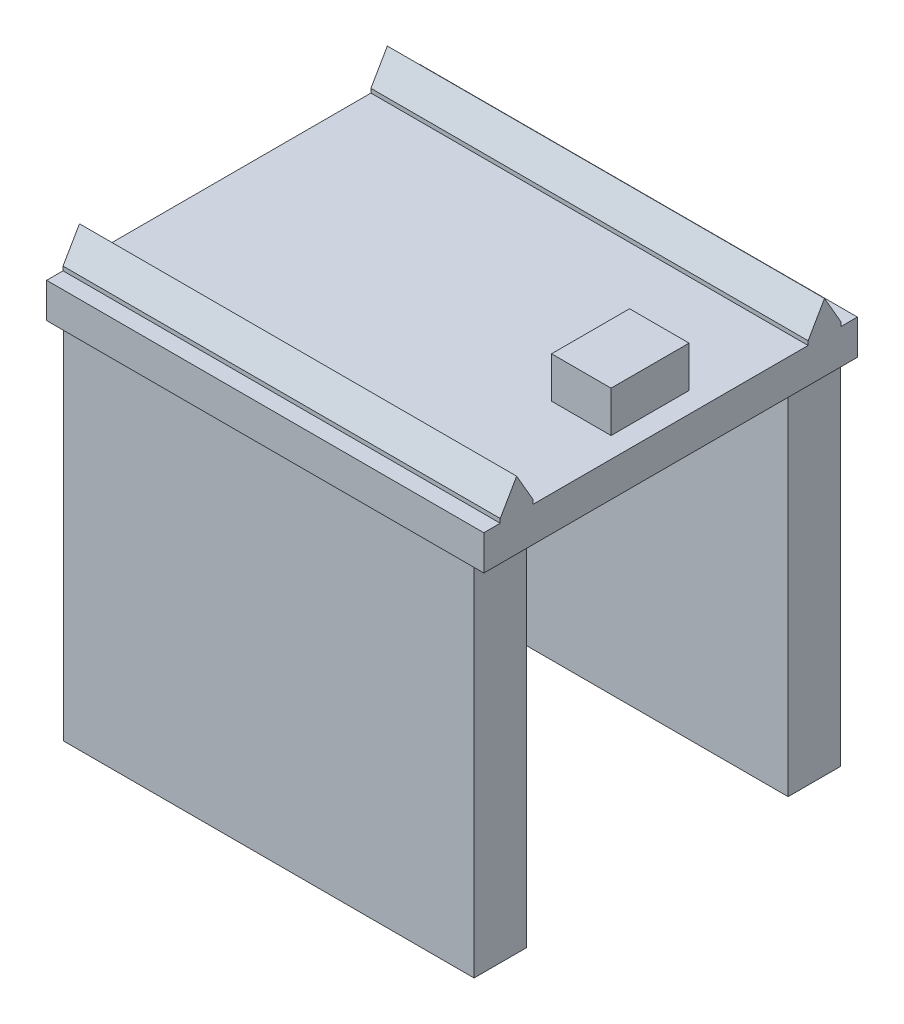
SolidWorks part; units mm, degrees
ref_plane "前视基准面" through (0, 0, 0) normal (0, 0, 1) x (1, 0, 0)
ref_plane "上视基准面" through (0, 0, 0) normal (0, 1, 0) x (1, 0, 0)
ref_plane "右视基准面" through (0, 0, 0) normal (1, 0, 0) x (0, 0, -1)
sketch "草图2" plane through (0, 0, 0) normal (0, 1, 0) x (1, 0, 0)
  line L1 (-10.65, 9.1) -> (10.65, 9.1)
  line L2 (-10.65, 9.1) -> (-10.65, -9.1)
  line L3 (-10.65, -9.1) -> (10.65, -9.1)
  line L4 (10.65, 9.1) -> (10.65, -9.1)
  line L5 (-10.65, 9.1) -> (10.65, -9.1) construction
  line L6 (-10.65, -9.1) -> (10.65, 9.1) construction
  point P0 (0, 0)
  dimension "D1" = 21.3
  dimension "D2" = 18.2
extrude "凸台-拉伸1" add sketch "草图2" along normal blind 1.7
sketch "草图4" plane through (0, 1.7, 0) normal (0, 1, 0) x (1, 0, 0)
  line L0 (-10.65, 9.1) -> (-10.65, -9.1) construction
  line L1 (-10.65, 8.3) -> (10.65, 8.3)
  line L2 (-10.65, 8.3) -> (-10.65, 6.7)
  line L3 (-10.65, 6.7) -> (10.65, 6.7)
  line L4 (10.65, 8.3) -> (10.65, 6.7)
  line L5 (10.65, -9.1) -> (10.65, 9.1) construction
  line L6 (0, 0) -> (10.65, 0) construction
  line L7 (10.65, 9.1) -> (-10.65, 9.1) construction
  line L8 (-10.65, -6.7) -> (10.65, -6.7)
  line L9 (10.65, -8.3) -> (10.65, -6.7)
  line L10 (-10.65, -8.3) -> (10.65, -8.3)
  line L11 (-10.65, -8.3) -> (-10.65, -6.7)
  dimension "D1" = 0.8
  dimension "D2" = 1.6
extrude "凸台-拉伸2" add sketch "草图4" along normal blind 1.6
chamfer "倒角1" distance 1.4 angle 30 4 edges at (0, 3.3, 8.3) (0, 3.3, 6.7) (0, 3.3, -6.7) (0, 3.3, -8.3) first distance on face at (0, 2.5, 8.3) first distance on face at (0, 2.5, 6.7) first distance on face at (0, 2.5, -6.7) first distance on face at (0, 2.5, -8.3)
sketch "草图5" plane through (0, 1.7, 0) normal (0, 1, 0) x (1, 0, 0)
  line L0 (0, 0) -> (10.65, 0) construction
  line L1 (10.65, -6.7) -> (10.65, 6.7) construction
  line L3 (6.75, 1.9) -> (9.65, 1.9)
  line L4 (6.75, 1.9) -> (6.75, -1.9)
  line L5 (6.75, -1.9) -> (9.65, -1.9)
  line L6 (9.65, 1.9) -> (9.65, -1.9)
  line L7 (6.75, 1.9) -> (9.65, -1.9) construction
  line L8 (6.75, -1.9) -> (9.65, 1.9) construction
  point P5 (8.2, 0)
  dimension "D1" = 2.9
  dimension "D2" = 3.8
  dimension "D3" = 3.9
extrude "凸台-拉伸3" add sketch "草图5" along normal blind 2
sketch "草图6" plane through (0, 0, 0) normal (0, -1, 0) x (1, 0, 0)
  line L0 (0, 0) -> (10.65, 0) construction
  line L1 (10.65, 9.1) -> (10.65, -9.1) construction
  line L2 (0, 0) -> (0, 9.1) construction
  line L3 (-10.65, 9.1) -> (10.65, 9.1) construction
  line L4 (-10, -6.375) -> (10, -6.375)
  line L5 (-10, 8.925) -> (10, 8.925)
  line L6 (-10, 8.925) -> (-10, 6.375)
  line L7 (-10, 6.375) -> (10, 6.375)
  line L8 (10, 8.925) -> (10, 6.375)
  line L9 (-10, 8.925) -> (10, 6.375) construction
  line L10 (-10, 6.375) -> (10, 8.925) construction
  line L11 (10, -8.925) -> (10, -6.375)
  line L12 (-10, -8.925) -> (10, -8.925)
  line L13 (-10, -8.925) -> (-10, -6.375)
  point P5 (0, 7.65)
  dimension "D1" = 17.85
  dimension "D2" = 20
  dimension "D3" = 2.55
extrude "凸台-拉伸4" add sketch "草图6" along normal blind 17.5
